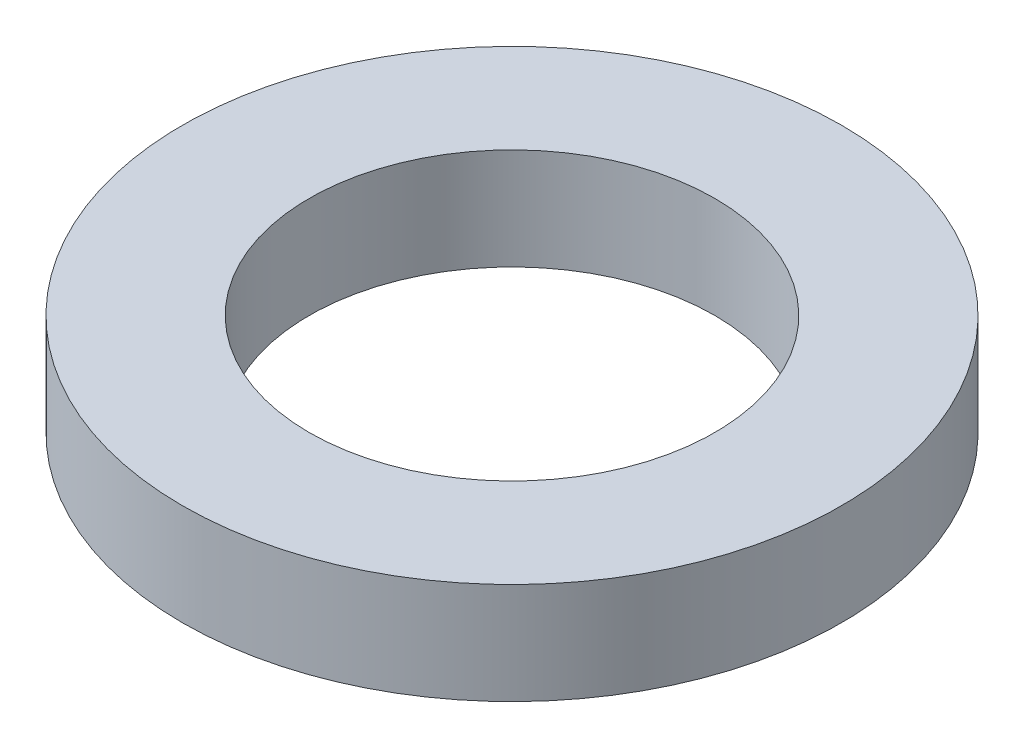
SolidWorks part; units mm, degrees
ref_plane "Front Plane" through (0, 0, 0) normal (0, 0, 1) x (1, 0, 0)
ref_plane "Top Plane" through (0, 0, 0) normal (0, 1, 0) x (1, 0, 0)
ref_plane "Right Plane" through (0, 0, 0) normal (1, 0, 0) x (0, 0, -1)
sketch "Sketch1" plane through (0, 0, 0) normal (0, 1, 0) x (1, 0, 0)
  circle A0 centre (0, 0) radius 65
  dimension "FLANGE_OD" = 130
extrude "Boss-Extrude1" add sketch "Sketch1" along normal blind 20
sketch "Sketch2" plane through (0, 0, 0) normal (0, 1, 0) x (1, 0, 0)
  circle A0 centre (0, 0) radius 40
  dimension "BORE_D" = 80
extrude "Cut-Extrude1" cut sketch "Sketch2" along normal through all
sketch "Sketch3" plane through (0, 20, 0) normal (0, 1, 0) x (1, 0, 0)
  circle A0 centre (0, 0) radius 29.6403 construction
  circle A1 centre (-29.6403, 0) radius 4.0242
  dimension "BOLT_D" = 8.0485
  dimension "BOLT_PCD" = 59.2806
extrude "Cut-Extrude2" cut sketch "Sketch3" against normal blind 14.7462 rebuild error yes
pattern_circular "CirPattern1" count 6 over 360 rebuild error yes
